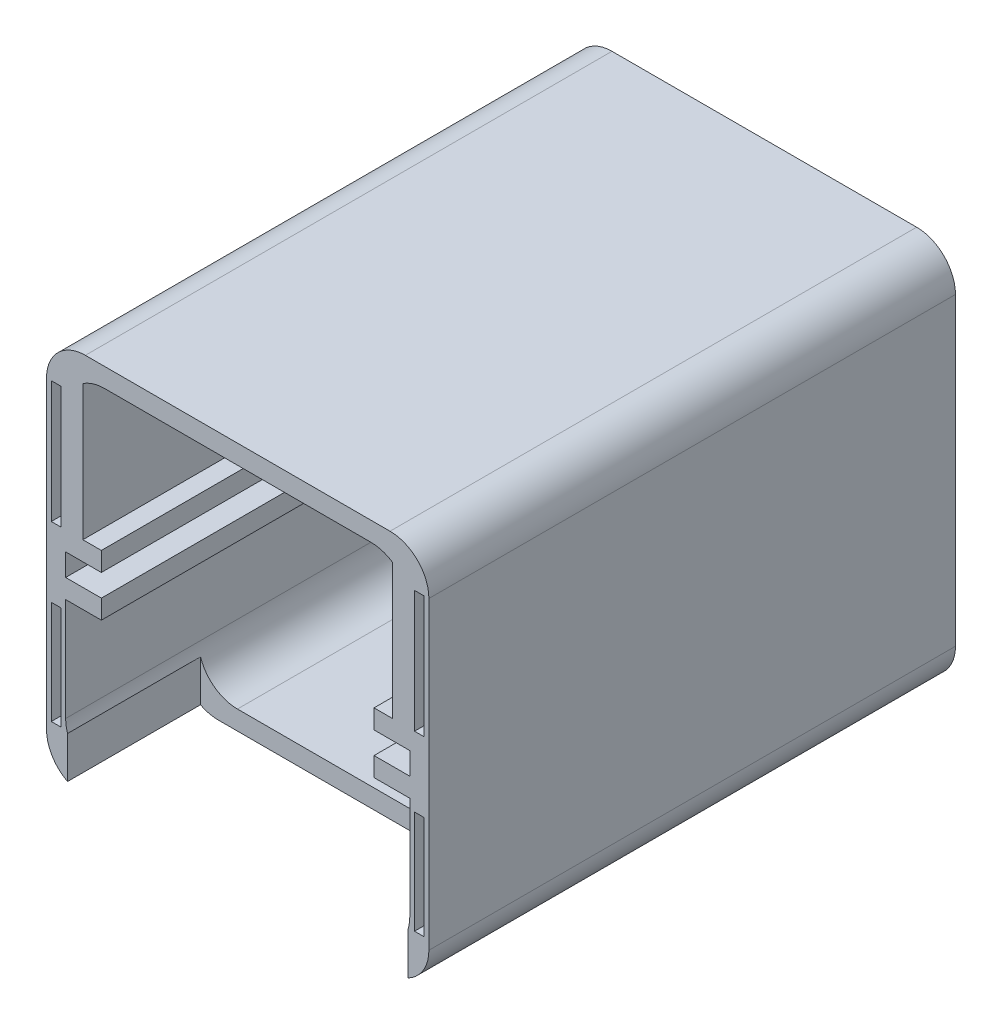
SolidWorks part; units mm, degrees
ref_plane "Front Plane" through (0, 0, 0) normal (0, 0, 1) x (1, 0, 0)
ref_plane "Top Plane" through (0, 0, 0) normal (0, 1, 0) x (1, 0, 0)
ref_plane "Right Plane" through (0, 0, 0) normal (1, 0, 0) x (0, 0, -1)
sketch "Sketch1" plane through (0, 0, 0) normal (0, 0, 1) x (1, 0, 0)
  line L1 (0, 0) -> (100, 0)
  line L2 (0, 0) -> (0, 100)
  line L3 (0, 100) -> (100, 100)
  line L4 (100, 0) -> (100, 100)
  line L5 (3, 3) -> (97, 3)
  line L6 (3, 3) -> (3, 97)
  line L7 (3, 97) -> (97, 97)
  line L8 (97, 3) -> (97, 97)
  dimension "D1" = 100
  dimension "D2" = 100
  dimension "D3" = 3
  dimension "D4" = 3
  dimension "D5" = 3
  dimension "D6" = 3
extrude "Boss-Extrude1" add sketch "Sketch1" along normal blind 250 contours L2 L1 L4 L3
sketch "Sketch2" plane through (0, 0, 0) normal (0, 0, -1) x (-1, 0, 0)
  line L1 (-95, 5) -> (-5, 5)
  line L2 (-95, 5) -> (-95, 95)
  line L3 (-95, 95) -> (-5, 95)
  line L4 (0, 100) -> (-100, 100)
  line L5 (-100, 100) -> (-100, 0)
  line L6 (-100, 0) -> (0, 0)
  line L7 (0, 0) -> (0, 100)
  line L8 (0, 100) -> (-100, 100)
  line L9 (-100, 100) -> (-100, 0)
  line L10 (-100, 0) -> (0, 0)
  line L11 (0, 0) -> (0, 100)
  line L12 (-5, 5) -> (-5, 95)
  dimension "D2" = 5
  dimension "D3" = 5
  dimension "D4" = 5
  dimension "D5" = 5
  dimension "D1" = 0
extrude "Cut-Extrude1" cut sketch "Sketch2" against normal through all contours L2 L1 L12 L3
fillet "Fillet1" radius 10.16 4 edges at (0, 100, 125) (0, 0, 125) (100, 100, 125) (100, 0, 125)
sketch "Sketch3" plane through (0, 0, 0) normal (0, 0, -1) x (-1, 0, 0)
  line L0 (-95, 50) -> (-5, 50) construction
  line L1 (-95, 5) -> (-95, 95) construction
  line L2 (-5, 5) -> (-5, 95) construction
  line L3 (-95, 57.9) -> (-85.6588, 57.9)
  line L4 (-85.6588, 57.9) -> (-85.6588, 52.9)
  line L5 (-85.6588, 52.9) -> (-95, 52.9)
  line L6 (-95, 52.9) -> (-95, 50)
  line L7 (-95, 50) -> (-95, 47.1)
  line L8 (-95, 47.1) -> (-85.6588, 47.1)
  line L9 (-85.6588, 47.1) -> (-85.6588, 42.1)
  line L10 (-85.6588, 42.1) -> (-95, 42.1)
  line L11 (-95, 42.1) -> (-95, 47.1)
  line L12 (-95, 57.9) -> (-95, 52.9)
  line L13 (-50, 67.1729) -> (-50, 35.9029) construction
  line L14 (-5, 42.1) -> (-5, 47.1)
  line L15 (-14.3412, 42.1) -> (-5, 42.1)
  line L16 (-14.3412, 47.1) -> (-14.3412, 42.1)
  line L17 (-5, 47.1) -> (-14.3412, 47.1)
  line L18 (-5, 57.9) -> (-5, 52.9)
  line L19 (-5, 57.9) -> (-14.3412, 57.9)
  line L20 (-14.3412, 57.9) -> (-14.3412, 52.9)
  line L21 (-14.3412, 52.9) -> (-5, 52.9)
  point P8 (-50, 50)
  dimension "D1" = 9.3412
  dimension "D2" = 5
  dimension "D3" = 5
  dimension "D4" = 5.8
  dimension "D5" = 2.9
extrude "Boss-Extrude2" add sketch "Sketch3" against normal through all contours L5 L4 L3 L12 | L8 L9 L10 L11 | L18 L21 L20 L19 | L14 L17 L16 L15
sketch "Sketch4" plane through (0, 100, 0) normal (0, 1, 0) x (1, 0, 0)
  line L0 (100, 0) -> (100, -250) construction
  line L1 (0, 0) -> (100, 0)
  line L2 (0, 0) -> (0, -125)
  line L3 (0, -125) -> (100, -125)
  line L4 (100, 0) -> (100, -125)
  dimension "D1" = 125
extrude "Cut-Extrude2" cut sketch "Sketch4" against normal through all
sketch "Sketch6" plane through (0, 5, 0) normal (0, 1, 0) x (1, 0, 0)
  line L0 (5, -250) -> (5, -125) construction
  line L1 (95, -125) -> (5, -125)
  line L2 (95, -125) -> (95, -130.08)
  line L3 (95, -130.08) -> (5, -130.08)
  line L4 (5, -125) -> (5, -130.08)
  dimension "D1" = 5.08
extrude "Boss-Extrude3" add sketch "Sketch6" along normal through all
sketch "Sketch7" plane through (0, 0, 125) normal (0, 0, -1) x (-1, 0, 0)
  line L0 (-50, 100) -> (-50, 0) construction
  line L1 (-5, 100) -> (-95, 100) construction
  line L2 (-10.16, 0) -> (-89.84, 0) construction
  line L3 (-100, 50) -> (0, 50) construction
  line L4 (-100, 10.16) -> (-100, 89.84) construction
  line L5 (0, 10.16) -> (0, 89.84) construction
  circle A0 centre (-50, 50) radius 45.3
  circle A1 centre (-50, 50) radius 48.3
  dimension "D1" = 96.6
  dimension "D2" = 90.6
extrude "Cut-Extrude4" cut sketch "Sketch7" against normal blind 5.08 contours A0
sketch "Sketch8" plane through (0, 0, 125) normal (0, 0, -1) x (-1, 0, 0)
  line L6 (-5, 100) -> (-95, 100)
  line L7 (-95, 100) -> (-95, 98.5921)
  line L8 (-100, 89.84) -> (-100, 10.16)
  line L9 (-89.84, 0) -> (-10.16, 0)
  line L10 (0, 10.16) -> (0, 89.84)
  line L11 (-5, 98.5921) -> (-5, 100)
  line L12 (-5, 100) -> (-95, 100)
  line L13 (-95, 100) -> (-95, 98.5921)
  line L14 (-100, 89.84) -> (-100, 10.16)
  line L15 (-89.84, 0) -> (-10.16, 0)
  line L16 (0, 10.16) -> (0, 89.84)
  line L17 (-5, 98.5921) -> (-5, 100)
  circle A0 centre (-50, 50) radius 45.3
  circle A1 centre (-50, 50) radius 45.3 construction
  arc A4 (-95, 98.5921) -> (-100, 89.84) centre (-89.84, 89.84) ccw
  arc A5 (-100, 10.16) -> (-89.84, 0) centre (-89.84, 10.16) ccw
  arc A6 (-10.16, 0) -> (0, 10.16) centre (-10.16, 10.16) ccw
  arc A7 (0, 89.84) -> (-5, 98.5921) centre (-10.16, 89.84) ccw
  arc A8 (-95, 98.5921) -> (-100, 89.84) centre (-89.84, 89.84) ccw
  arc A9 (-100, 10.16) -> (-89.84, 0) centre (-89.84, 10.16) ccw
  arc A10 (-10.16, 0) -> (0, 10.16) centre (-10.16, 10.16) ccw
  arc A11 (0, 89.84) -> (-5, 98.5921) centre (-10.16, 89.84) ccw
  dimension "D1" = 0
sketch "Sketch10" plane through (0, 0, 125) normal (0, 0, -1) x (-1, 0, 0)
  line L6 (-5, 100) -> (-95, 100)
  line L7 (-95, 100) -> (-95, 98.5921)
  line L8 (-100, 89.84) -> (-100, 10.16)
  line L9 (-89.84, 0) -> (-10.16, 0)
  line L10 (0, 10.16) -> (0, 89.84)
  line L11 (-5, 98.5921) -> (-5, 100)
  line L12 (-5, 100) -> (-95, 100)
  line L13 (-95, 100) -> (-95, 98.5921)
  line L14 (-100, 89.84) -> (-100, 10.16)
  line L15 (-89.84, 0) -> (-10.16, 0)
  line L16 (0, 10.16) -> (0, 89.84)
  line L17 (-5, 98.5921) -> (-5, 100)
  circle A0 centre (-50, 50) radius 48.3
  circle A1 centre (-50, 50) radius 45.3
  circle A2 centre (-50, 50) radius 45.3 construction
  arc A4 (-95, 98.5921) -> (-100, 89.84) centre (-89.84, 89.84) ccw
  arc A5 (-100, 10.16) -> (-89.84, 0) centre (-89.84, 10.16) ccw
  arc A6 (-10.16, 0) -> (0, 10.16) centre (-10.16, 10.16) ccw
  arc A7 (0, 89.84) -> (-5, 98.5921) centre (-10.16, 89.84) ccw
  arc A8 (-95, 98.5921) -> (-100, 89.84) centre (-89.84, 89.84) ccw
  arc A9 (-100, 10.16) -> (-89.84, 0) centre (-89.84, 10.16) ccw
  arc A10 (-10.16, 0) -> (0, 10.16) centre (-10.16, 10.16) ccw
  arc A11 (0, 89.84) -> (-5, 98.5921) centre (-10.16, 89.84) ccw
  dimension "D2" = 96.6
  dimension "D1" = 0
extrude "Boss-Extrude4" add sketch "Sketch10" along normal blind 30 contours A0
sketch "Sketch11" plane through (0, 0, 95) normal (0, 0, -1) x (-1, 0, 0)
  circle A1 centre (-50, 50) radius 45.3
  circle A2 centre (-50, 50) radius 45.3 construction
extrude "Cut-Extrude5" cut sketch "Sketch11" against normal up to surface (30 mm away) up to face at (98.3, 50, 125)
fillet "Fillet2" [suppressed] radius 2.54
sketch "Sketch13" plane through (0, 0, 0) normal (0, -1, 0) x (1, 0, 0)
  line L0 (10.16, 250) -> (89.84, 250) construction
  line L1 (81.75, 250) -> (18.25, 250)
  line L2 (81.75, 250) -> (81.75, 186.5)
  line L3 (81.75, 186.5) -> (18.25, 186.5)
  line L4 (18.25, 250) -> (18.25, 186.5)
  point P6 (50, 250)
  point P7 (50, 250)
  dimension "D1" = 63.5
  dimension "D2" = 63.5
extrude "Cut-Extrude7" cut sketch "Sketch13" against normal up to surface (5 mm away) up to face at (50, 5, 170.0533)
fillet "Fillet4" radius 1.27 3 edges at (18.25, 0, 218.25) (50, 0, 186.5) (81.75, 0, 218.25)
fillet "Fillet5" radius 10.16 4 edges at (95, 95, 190.04) (95, 5, 190.04) (5, 95, 190.04) (5, 5, 190.04)
sketch "Sketch14" plane through (0, 0, 125) normal (0, 0, -1) x (-1, 0, 0)
  line L0 (-50, 95.3) -> (-50, 50) construction
  line L6 (-5, 100) -> (-95, 100)
  line L7 (-95, 100) -> (-95, 98.5921)
  line L8 (-100, 89.84) -> (-100, 10.16)
  line L9 (-89.84, 0) -> (-10.16, 0)
  line L10 (0, 10.16) -> (0, 89.84)
  line L11 (-5, 98.5921) -> (-5, 100)
  line L12 (-5, 100) -> (-95, 100)
  line L13 (-95, 100) -> (-95, 98.5921)
  line L14 (-100, 89.84) -> (-100, 10.16)
  line L15 (-89.84, 0) -> (-10.16, 0)
  line L16 (0, 10.16) -> (0, 89.84)
  line L17 (-5, 98.5921) -> (-5, 100)
  circle A0 centre (-50, 50) radius 45.3 construction
  circle A1 centre (-50, 50) radius 48.3
  circle A2 centre (-50, 50) radius 48.3 construction
  arc A4 (-95, 98.5921) -> (-100, 89.84) centre (-89.84, 89.84) ccw
  arc A5 (-100, 10.16) -> (-89.84, 0) centre (-89.84, 10.16) ccw
  arc A6 (-10.16, 0) -> (0, 10.16) centre (-10.16, 10.16) ccw
  arc A7 (0, 89.84) -> (-5, 98.5921) centre (-10.16, 89.84) ccw
  arc A8 (-95, 98.5921) -> (-100, 89.84) centre (-89.84, 89.84) ccw
  arc A9 (-100, 10.16) -> (-89.84, 0) centre (-89.84, 10.16) ccw
  arc A10 (-10.16, 0) -> (0, 10.16) centre (-10.16, 10.16) ccw
  arc A11 (0, 89.84) -> (-5, 98.5921) centre (-10.16, 89.84) ccw
  dimension "D1" = 0
ref_plane "Plane1" through (14.3412, 52.9, 250) normal (0, 0, -1) x (-1, 0, 0)
extrude "Boss-Extrude6" add sketch "Sketch14" along direction (0, 0, 1) on the side of the normal up to surface (30 mm away) contours L12 L13 A8 L14 A9 L15 A10 L16 A11 L17 up to face at (4.7, 50, 95)
sketch "Sketch16" plane through (0, 0, 125) normal (0, 0, 1) x (1, 0, 0)
  circle A1 centre (50, 50) radius 45.3
  circle A2 centre (50, 50) radius 45.3
  dimension "D1" = 0
extrude "Cut-Extrude8" cut sketch "Sketch16" against normal through all
sketch "Sketch18" plane through (0, 0, 95) normal (0, 0, -1) x (-1, 0, 0)
  line L1 (-100, 89.84) -> (-100, 107.62)
  line L2 (-100, 107.62) -> (0, 107.62)
  line L3 (0, 107.62) -> (0, 89.84)
  line L4 (-5, 100) -> (-95, 100) construction
  line L5 (-89.84, 100) -> (-10.16, 100)
  arc A4 (-100, 89.84) -> (-89.84, 100) centre (-89.84, 89.84) cw
  arc A10 (-95, 98.5921) -> (-100, 89.84) centre (-89.84, 89.84) ccw construction
  arc A11 (0, 89.84) -> (-10.16, 100) centre (-10.16, 89.84) ccw
  arc A12 (0, 89.84) -> (-5, 98.5921) centre (-10.16, 89.84) ccw construction
  dimension "D1" = 7.62
extrude "Cut-Extrude10" cut sketch "Sketch18" against normal through all
sketch "Sketch19" plane through (0, 0, 0) normal (0, -1, 0) x (1, 0, 0)
  line L0 (83.02, 250) -> (89.84, 250) construction
  line L1 (90.5, 250) -> (9.5, 250)
  line L2 (90.5, 250) -> (90.5, 185.23)
  line L3 (90.5, 185.23) -> (9.5, 185.23)
  line L4 (9.5, 250) -> (9.5, 185.23)
  line L5 (84.84, 250) -> (15.16, 250) construction
  line L8 (83.02, 185.23) -> (16.98, 185.23) construction
  point P8 (50, 250)
  point P9 (50, 250)
  dimension "D1" = 81
extrude "Cut-Extrude11" cut sketch "Sketch19" against normal blind 25.4
sketch "Sketch20" plane through (0, 0, 0) normal (0, -1, 0) x (1, 0, 0)
  line L0 (9.5, 250) -> (9.5, 185.23) construction
  line L1 (9.5, 217.73) -> (90.5, 217.73)
  line L2 (9.5, 217.73) -> (9.5, 185.23)
  line L3 (9.5, 185.23) -> (90.5, 185.23)
  line L4 (90.5, 217.73) -> (90.5, 185.23)
  line L5 (90.5, 185.23) -> (90.5, 250) construction
  line L6 (89.84, 185.23) -> (10.16, 185.23) construction
  dimension "D1" = 32.5
extrude "Boss-Extrude7" add sketch "Sketch20" against normal up to surface (5 mm away) contours L2 L1 L4 L3 up to face at (50, 5, 148.4633)
sketch "Sketch21" plane through (0, 0, 185.23) normal (0, 0, 1) x (1, 0, 0)
  line L0 (15.16, 5) -> (15.16, 0)
  line L1 (15.16, 0) -> (9.5, 0)
  line L2 (84.84, 5) -> (90.5, 5)
  line L3 (90.5, 5) -> (90.5, 6.7226)
  line L4 (84.84, 5) -> (90.5, 5)
  line L5 (90.5, 5) -> (90.5, 6.7226)
  line L6 (9.5, 5) -> (15.16, 5)
  line L7 (9.5, 6.7226) -> (9.5, 5)
  line L8 (9.5, 5) -> (15.16, 5)
  line L9 (9.5, 6.7226) -> (9.5, 5)
  line L10 (84.84, 5) -> (84.84, 0)
  line L11 (84.84, 0) -> (90.5, 0)
  line L14 (90.5, 0.0215) -> (90.5, 5)
  line L15 (90.5, 5) -> (9.5, 5)
  line L16 (9.5, 5) -> (9.5, 0.0215)
  line L17 (9.5, 0.0215) -> (9.5, 0)
  line L18 (9.5, 0) -> (90.5, 0)
  line L19 (90.5, 0) -> (90.5, 0.0215)
  line L20 (90.5, 0.0215) -> (90.5, 5)
  line L21 (90.5, 5) -> (9.5, 5)
  line L22 (9.5, 5) -> (9.5, 0.0215)
  line L23 (9.5, 0.0215) -> (9.5, 0)
  line L24 (9.5, 0) -> (90.5, 0)
  line L25 (90.5, 0) -> (90.5, 0.0215)
  arc A1 (84.84, 5) -> (90.5, 6.7226) centre (84.84, 15.16) ccw
  arc A2 (84.84, 5) -> (90.5, 6.7226) centre (84.84, 15.16) ccw
  arc A3 (9.5, 6.7226) -> (15.16, 5) centre (15.16, 15.16) ccw
  arc A4 (9.5, 6.7226) -> (15.16, 5) centre (15.16, 15.16) ccw
  line M13 (84.84, 5) -> (90.5, 5)
  line M14 (90.5, 5) -> (90.5, 6.7226)
  arc M15 (90.5, 6.7226) -> (84.84, 5) centre (84.84, 15.16) cw
  dimension "D1" = 0
  dimension "D2" = 0
  dimension "D3" = 0
extrude "Boss-Extrude8" add sketch "Sketch21" along normal up to surface (32.5 mm away) contours M15 M13 M14 | A4 L8 L9 region at (89.1101, 5.5083, 185.23) up to face at (50, 1.6738, 217.73)
sketch "Sketch24" plane through (0, 0, 130.08) normal (0, 0, 1) x (1, 0, 0)
  line L0 (5, 57.9) -> (5, 84.84) construction
  line L1 (95, 57.9) -> (86.75, 57.9)
  line L2 (95, 57.9) -> (95, 95)
  line L3 (95, 95) -> (5, 95)
  line L4 (5, 57.9) -> (5, 95)
  line L5 (84.84, 95) -> (15.16, 95) construction
  line L6 (10.16, 100) -> (89.84, 100) construction
  line L8 (86.75, 57.9) -> (86.75, 92.9)
  line L9 (86.75, 92.9) -> (13.25, 92.9)
  line L10 (13.25, 57.9) -> (13.25, 92.9)
  line L11 (13.25, 57.9) -> (5, 57.9)
  point P15 (50, 100)
  point P16 (50, 92.9)
  dimension "D1" = 73.5
  dimension "D2" = 35
extrude "Boss-Extrude10" add sketch "Sketch24" along normal up to surface (119.92 mm away) contours L1 L8 L9 L10 L11 L4 L3 L2 up to face at (50, 50.2195, 250)
sketch "Sketch25" plane through (0, 0, 130.08) normal (0, 0, 1) x (1, 0, 0)
  line L1 (13.25, 92.9) -> (86.75, 92.9)
  line L2 (13.25, 92.9) -> (13.25, 76.4864)
  line L3 (13.25, 76.4864) -> (86.75, 76.4864)
  line L4 (86.75, 92.9) -> (86.75, 76.4864)
extrude "Boss-Extrude11" add sketch "Sketch25" along normal blind 6.35 contours L2 L1 L4 L3
sketch "Sketch26" plane through (0, 0, 0) normal (-1, 0, 0) x (0, 0, 1)
  line L0 (95, 100) -> (250, 100) construction
  line L1 (95, 0) -> (112.272, 0)
  line L2 (95, 0) -> (95, 100)
  line L3 (95, 100) -> (112.272, 100)
  line L4 (112.272, 0) -> (112.272, 100)
  dimension "D1" = 17.272
extrude "Cut-Extrude12" cut sketch "Sketch26" against normal blind 132
sketch "Sketch28" plane through (0, 0, 250) normal (0, 0, 1) x (1, 0, 0)
  line L1 (9.5, 57.9) -> (90.5, 57.9)
  line L2 (9.5, 57.9) -> (9.5, 95.8)
  line L3 (9.5, 95.8) -> (90.5, 95.8)
  line L4 (90.5, 57.9) -> (90.5, 95.8)
  line L6 (86.75, 57.9) -> (85.6588, 57.9) construction
  line L8 (0, 10.16) -> (0, 89.84) construction
  line L9 (100, 10.16) -> (100, 89.84) construction
  line L10 (13.25, 57.9) -> (14.3412, 57.9) construction
  dimension "D1" = 81
  dimension "D2" = 37.9
  dimension "D3" = 9.5
  dimension "D4" = 9.5
  dimension "D5" = 0
extrude "Cut-Extrude13" cut sketch "Sketch28" against normal blind 113.57
sketch "Sketch29" plane through (0, 0, 250) normal (0, 0, 1) x (1, 0, 0)
  line L0 (0, 10.16) -> (0, 89.84) construction
  line L1 (3.75, 57.9) -> (1.25, 57.9)
  line L2 (3.75, 57.9) -> (3.75, 89.8)
  line L3 (3.75, 89.8) -> (1.25, 89.8)
  line L4 (1.25, 57.9) -> (1.25, 89.8)
  line L5 (9.5, 95.8) -> (9.5, 57.9) construction
  line L6 (9.5, 57.9) -> (13.25, 57.9) construction
  line L7 (90.5, 95.8) -> (9.5, 95.8) construction
  line L10 (5, 15.16) -> (5, 42.1) construction
  line L11 (1.25, 12.6) -> (3.75, 12.6)
  line L12 (1.25, 12.6) -> (1.25, 39.6)
  line L13 (1.25, 39.6) -> (3.75, 39.6)
  line L14 (3.75, 12.6) -> (3.75, 39.6)
  line L15 (14.3412, 42.1) -> (5, 42.1) construction
  line L24 (98.75, 39.6) -> (96.25, 39.6)
  line L25 (96.25, 12.6) -> (96.25, 39.6)
  line L26 (98.75, 12.6) -> (96.25, 12.6)
  line L27 (98.75, 12.6) -> (98.75, 39.6)
  line L32 (96.25, 89.8) -> (98.75, 89.8)
  line L33 (98.75, 57.9) -> (98.75, 89.8)
  line L34 (96.25, 57.9) -> (98.75, 57.9)
  line L35 (96.25, 57.9) -> (96.25, 89.8)
  dimension "D1" = 2.5
  dimension "D2" = 5.75
  dimension "D3" = 0
  dimension "D4" = 6
  dimension "D5" = 1.25
  dimension "D6" = 1.25
  dimension "D7" = 2.5
  dimension "D8" = 27
  dimension "D9" = 31.9
  dimension "D10" = 1.25
extrude "Cut-Extrude14" cut sketch "Sketch29" against normal blind 40
sketch "Sketch30" plane through (0, 0, 250) normal (0, 0, 1) x (1, 0, 0)
  line L0 (50, 0) -> (50, 100) construction
  line L1 (95, 57.9) -> (5, 57.9)
  line L2 (95, 57.9) -> (95, 95.8)
  line L3 (95, 95.8) -> (5, 95.8)
  line L4 (5, 57.9) -> (5, 95.8)
  line L5 (9.5, 0) -> (90.5, 0) construction
  line L6 (10.16, 100) -> (89.84, 100) construction
  line L11 (90.5, 57.9) -> (85.6588, 57.9) construction
  line L12 (90.5, 95.8) -> (9.5, 95.8) construction
  point P10 (50, 57.9)
  dimension "D1" = 90
extrude "Cut-Extrude15" cut sketch "Sketch30" against normal up to surface (119.92 mm away) and the other way through all up to face at (10.6416, 53.0314, 130.08)
sketch "Sketch32" plane through (0, 0, 130.08) normal (0, 0, 1) x (1, 0, 0)
  line L0 (5, 95.8) -> (5, 57.9) construction
  line L1 (15.16, 95) -> (84.84, 95)
  line L2 (95, 57.9) -> (95, 95.8) construction
  line L3 (95, 84.84) -> (95, 95.8)
  line L4 (95, 95.8) -> (5, 95.8)
  line L5 (5, 95.8) -> (5, 84.84)
  arc A0 (5, 84.84) -> (15.16, 95) centre (15.16, 84.84) cw
  arc A1 (84.84, 95) -> (95, 84.84) centre (84.84, 84.84) cw
  dimension "D1" = 10.16
  dimension "D2" = 10.16
  dimension "D3" = 0.8
  dimension "D4" = 10.16
  dimension "D5" = 10.16
  dimension "D6" = 10.16
  dimension "D7" = 10.16
extrude "Boss-Extrude12" add sketch "Sketch32" along normal up to surface (119.92 mm away) up to face at (50, 47.8245, 250)
sketch "Sketch33" plane through (0, 0, 0) normal (0, -1, 0) x (1, 0, 0)
  line L0 (-18.6368, 250) -> (47.3192, 250) construction
  line L1 (5.5, 250) -> (94.5, 250)
  line L2 (5.5, 250) -> (5.5, 215.23)
  line L3 (5.5, 215.23) -> (94.5, 215.23)
  line L4 (94.5, 250) -> (94.5, 215.23)
  line L5 (9.5, 217.73) -> (90.5, 217.73) construction
  line L6 (90.5, 217.73) -> (90.5, 250) construction
  line L7 (9.5, 250) -> (9.5, 217.73) construction
  dimension "D1" = 2.5
  dimension "D2" = 4
  dimension "D3" = 4
extrude "Cut-Extrude16" cut sketch "Sketch33" against normal up to surface (42.1 mm away) up to face at (8.8153, 42.1, 178.048)
sketch "Sketch35" plane through (0, 0, 250) normal (0, 0, 1) x (1, 0, 0)
  line L0 (10.16, 100) -> (89.84, 100) construction
  line L1 (5, 57.9) -> (9.5, 57.9)
  line L2 (5, 57.9) -> (5, 96)
  line L3 (5, 96) -> (9.5, 96)
  line L4 (9.5, 57.9) -> (9.5, 96)
  line L5 (95, 57.9) -> (90.5, 57.9)
  line L6 (95, 57.9) -> (95, 96)
  line L7 (95, 96) -> (90.5, 96)
  line L8 (90.5, 57.9) -> (90.5, 96)
  dimension "D1" = 4.5
  dimension "D2" = 4.5
  dimension "D3" = 4
  dimension "D4" = 4
extrude "Boss-Extrude14" add sketch "Sketch35" against normal up to surface (119.92 mm away) contours L6 L5 L8 L7 | L2 L1 L4 L3 up to face at (13.4192, 79.8549, 130.08)
